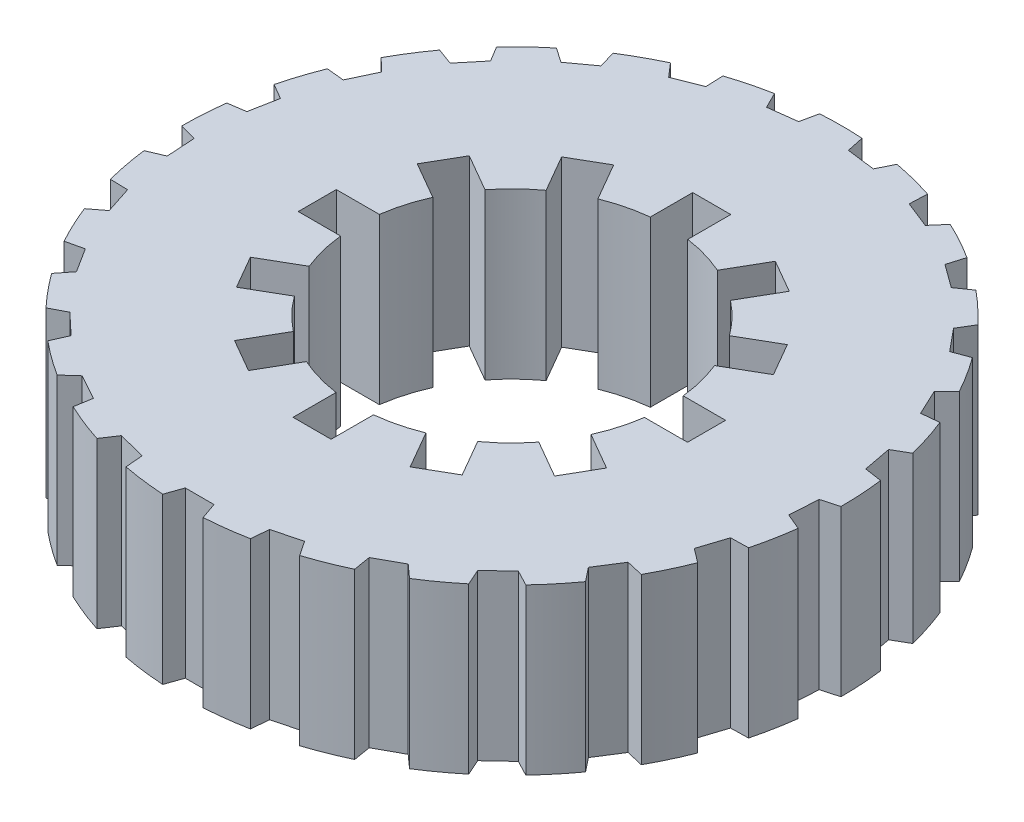
SolidWorks part; units mm, degrees
ref_plane "Front Plane" through (0, 0, 0) normal (0, 0, 1) x (1, 0, 0)
ref_plane "Top Plane" through (0, 0, 0) normal (0, 1, 0) x (1, 0, 0)
ref_plane "Right Plane" through (0, 0, 0) normal (1, 0, 0) x (0, 0, -1)
sketch "Sketch1" plane through (0, 0, 0) normal (0, 1, 0) x (1, 0, 0)
  circle A0 centre (0, 0) radius 38.1
extrude "Boss-Extrude1" add sketch "Sketch1" along normal blind 19.05
sketch "Sketch2" plane through (0, 0, 0) normal (0, -1, 0) x (1, 0, 0)
  line L10 (0, 38.1) -> (-2.36, 38.1)
  line L11 (0, 38.1) -> (2.36, 38.1)
  line L12 (0, 36.1) -> (-1.66, 36.1)
  line L13 (0, 36.1) -> (1.66, 36.1)
  line L14 (-2.36, 38.1) -> (-1.66, 36.1)
  line L15 (2.36, 38.1) -> (1.66, 36.1)
  circle A0 centre (0, 0) radius 38.1 construction
  dimension "D1" = 2.36
  dimension "D2" = 2.36
  dimension "D3" = 1.66
  dimension "D4" = 1.66
  dimension "D5" = 2
extrude "Cut-Extrude1" cut sketch "Sketch2" against normal blind 33
pattern_circular "CirPattern1" count 25 over 360 about axis through (0, 0, 0) along (0, 1, 0) of "Cut-Extrude1"
sketch "Sketch3" plane through (0, 19.05, 0) normal (0, 1, 0) x (1, 0, 0)
  line L16 (-1.9, 22.8) -> (-1.9, 17.8994)
  line L17 (0.3, 22.8) -> (-1.9, 22.8)
  line L18 (0.3, 22.8) -> (2.5, 22.8)
  line L19 (2.5, 22.8) -> (2.5, 17.8255)
  circle A1 centre (0, 0) radius 18
extrude "Cut-Extrude2" cut sketch "Sketch3" against normal blind 28 contours A1 region at (0, 19.05, 0)
extrude "Cut-Extrude8" cut sketch "Sketch3<7>" against normal blind 23 contours A1 region at (0.3056, 19.05, -20.3761)
sketch "Sketch3<7>" plane through (0, 19.05, 0) normal (0, 1, 0) x (1, 0, 0) same geometry as "Sketch3"
pattern_circular "CirPattern2" count 12 every 30 about axis through (0, 19.05, 0) along (0, 1, 0) of "Cut-Extrude8"
